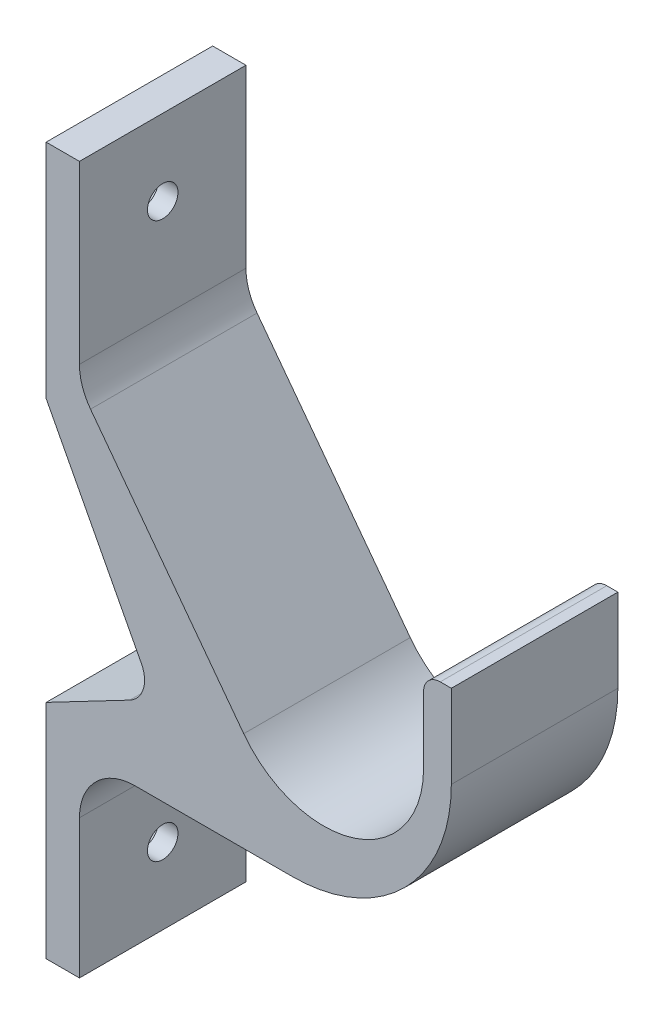
SolidWorks part; units mm, degrees
ref_plane "Front Plane" through (0, 0, 0) normal (0, 0, 1) x (1, 0, 0)
ref_plane "Top Plane" through (0, 0, 0) normal (0, 1, 0) x (1, 0, 0)
ref_plane "Right Plane" through (0, 0, 0) normal (1, 0, 0) x (0, 0, -1)
sketch "Sketch5" [suppressed] plane through (0, 0, 0) normal (0, 0, 1) x (1, 0, 0)
  line L0 (0, 87.2417) -> (0, -75.2249) construction
  line L1 (0, -23.7065) -> (0, -63.7065)
  line L2 (-19.4883, 13.4984) -> (0, 23.7065) construction
  line L3 (-19.4883, 13.4984) -> (0, -23.7065) construction
  line L4 (0, -23.7065) -> (15.0591, -15.8184)
  line L5 (0, 23.7065) -> (17.1683, -9.0692)
  line L6 (-19.4883, 13.4984) -> (19.4883, -13.4984) construction
  line L7 (0, -23.7065) -> (0, 23.7065) construction
  line L8 (0, -63.7065) -> (6, -63.7065)
  line L9 (6, -63.7065) -> (6, -38.7065)
  line L10 (0, 23.7065) -> (0, 63.7065)
  line L11 (0, 63.7065) -> (6, 63.7065)
  line L12 (6, 63.7065) -> (6, 32.0372)
  line L13 (16, -28.7065) -> (44.2935, -28.7065)
  line L14 (73, 0) -> (73, 15)
  line L15 (73, 15) -> (71, 15)
  line L16 (68, 12) -> (68, 0)
  line L17 (7.9971, 26.0411) -> (35.5948, -10.793)
  arc A0 (15.0591, -15.8184) -> (17.1683, -9.0692) centre (12.7391, -11.3893) ccw
  arc A1 (44.2935, -28.7065) -> (73, 0) centre (44.2935, 0) ccw
  arc A2 (68, 0) -> (35.5948, -10.793) centre (50, 0) cw
  arc A3 (6, -38.7065) -> (16, -28.7065) centre (16, -38.7065) cw
  arc A4 (6, 32.0372) -> (7.9971, 26.0411) centre (16, 32.0372) ccw
  arc A5 (71, 15) -> (68, 12) centre (71, 12) ccw
  circle A6 centre (50, 0) radius 18
  arc A7 (73, 0) -> (54.4129, 22.5727) centre (50, 0) ccw
  spline S0 degree 3 poles (54.4129, 22.5727) (48.6988, 23.6898) (29.1828, 17.0843) (12.2664, 20.3429) (7.9971, 26.0411) knots 0 0 0 0 0.577741 1 1 1 1
  point P3 (0, 0)
  point P32 (6, -28.7065)
  point P35 (6, 28.7065)
  point P38 (68, 15)
  dimension "D3" = 5
  dimension "D8" = 18
  dimension "D13" = 10
  dimension "D14" = 3
  dimension "D1" = 22
  dimension "D2" = 42
  dimension "D4" = 40
  dimension "D5" = 40
  dimension "D6" = 6
  dimension "D7" = 35
  dimension "D9" = 5
  dimension "D10" = 15
  dimension "D11" = 35
  dimension "D12" = 50
extrude "Boss-Extrude2" [suppressed] add sketch "Sketch5" along normal mid plane 30
sketch "Sketch1" plane through (0, 0, 0) normal (0, 0, 1) x (1, 0, 0)
  line L0 (0, 87.2417) -> (0, -75.2249) construction
  line L1 (0, -23.7065) -> (0, -63.7065)
  line L2 (-19.4883, 13.4984) -> (0, 23.7065) construction
  line L3 (-19.4883, 13.4984) -> (0, -23.7065) construction
  line L4 (0, -23.7065) -> (15.0591, -15.8184)
  line L5 (0, 23.7065) -> (17.1683, -9.0692)
  line L6 (-19.4883, 13.4984) -> (19.4883, -13.4984) construction
  line L7 (0, -23.7065) -> (0, 23.7065) construction
  line L8 (0, -63.7065) -> (6, -63.7065)
  line L9 (6, -63.7065) -> (6, -38.7065)
  line L10 (0, 23.7065) -> (0, 63.7065)
  line L11 (0, 63.7065) -> (6, 63.7065)
  line L12 (6, 63.7065) -> (6, 32.0372)
  line L13 (16, -28.7065) -> (44.2935, -28.7065)
  line L14 (73, 0) -> (73, 15)
  line L15 (73, 15) -> (71, 15)
  line L16 (68, 12) -> (68, 0)
  line L17 (7.9971, 26.0411) -> (35.5948, -10.793)
  arc A0 (15.0591, -15.8184) -> (17.1683, -9.0692) centre (12.7391, -11.3893) ccw
  arc A1 (44.2935, -28.7065) -> (73, 0) centre (44.2935, 0) ccw
  arc A2 (68, 0) -> (35.5948, -10.793) centre (50, 0) cw
  arc A3 (6, -38.7065) -> (16, -28.7065) centre (16, -38.7065) cw
  arc A4 (6, 32.0372) -> (7.9971, 26.0411) centre (16, 32.0372) ccw
  arc A5 (71, 15) -> (68, 12) centre (71, 12) ccw
  point P3 (0, 0)
  point P32 (6, -28.7065)
  point P35 (6, 28.7065)
  point P38 (68, 15)
  dimension "D3" = 5
  dimension "D8" = 18
  dimension "D13" = 10
  dimension "D14" = 3
  dimension "D1" = 22
  dimension "D2" = 42
  dimension "D4" = 40
  dimension "D5" = 40
  dimension "D6" = 6
  dimension "D7" = 35
  dimension "D9" = 5
  dimension "D10" = 15
  dimension "D11" = 35
  dimension "D12" = 50
extrude "Boss-Extrude1" add sketch "Sketch1" along normal mid plane 30
sketch "Sketch4" plane through (0, 0, 0) normal (1, 0, 0) x (0, 0, -1)
  point P0 (0, 50)
  point P2 (0, -50)
  dimension "D1" = 50
  dimension "D2" = 50
hole_wizard "CSK for M5 Flat Head Machine Screw1" positions "Sketch4" profile "Sketch3" countersink size "M5" standard "ANSI Metric" end condition through all
sketch "Sketch3" plane through (0, 50, 0) normal (0, 1, 0) x (0, 0, 1)
  line L0 (0, 0) -> (0, 73)
  line L1 (0, 73) -> (2.75, 73)
  line L2 (2.75, 73) -> (2.75, 2.45)
  line L3 (2.75, 2.45) -> (5.2, 0)
  line L5 (5.2, 0) -> (0, 0)
  line L6 (-2.75, 2.45) -> (-5.2, 0) construction
  line L11 (0, -6.35) -> (0, 107.95) construction
  dimension "Thru Hole Dia." = 5.5
  dimension "Thru Hole Depth" = 73
  dimension "Near C'Sink Dia." = 10.4
  dimension "Near C'Sink Angle" = 90
